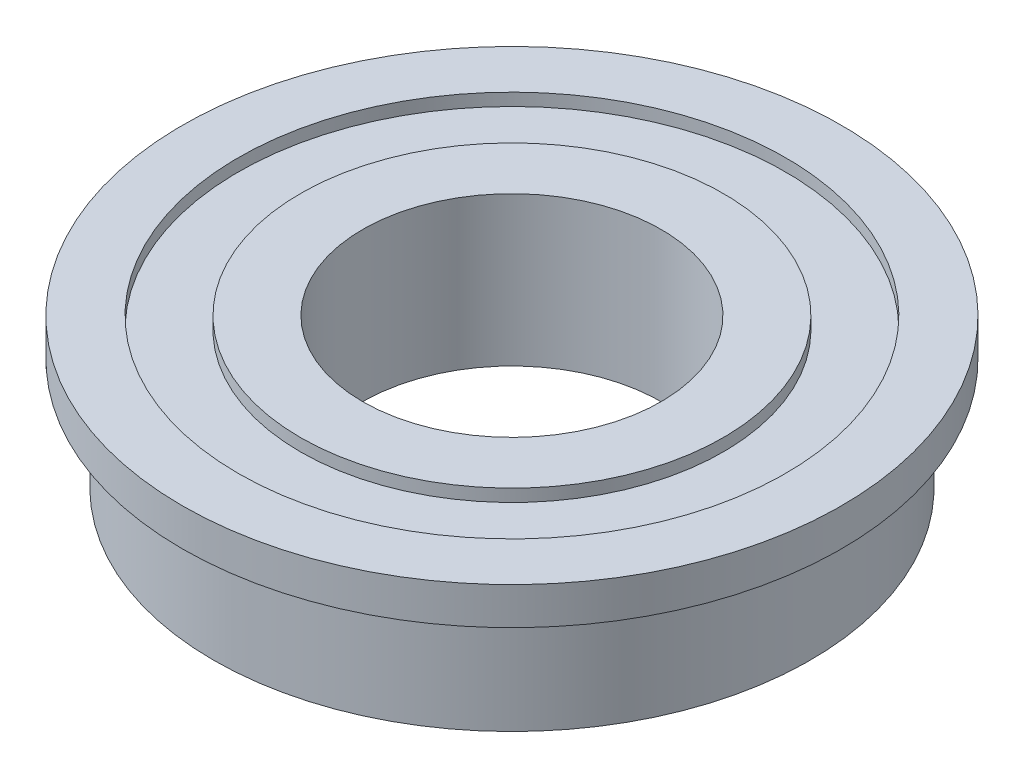
SolidWorks part; units mm, degrees
material "AISI 316 Stainless Steel Sheet (SS)"
ref_plane "Front Plane" through (0, 0, 0) normal (0, 0, 1) x (1, 0, 0)
ref_plane "Top Plane" through (0, 0, 0) normal (0, 1, 0) x (1, 0, 0)
ref_plane "Right Plane" through (0, 0, 0) normal (1, 0, 0) x (0, 0, -1)
sketch "Sketch1" plane through (0, 0, 0) normal (0, 1, 0) x (1, 0, 0)
  circle A0 centre (0, 0) radius 12
  circle A1 centre (0, 0) radius 13.25
  circle A2 centre (0, 0) radius 6
  dimension "D1" = 26.5
  dimension "D2" = 24
  dimension "D3" = 12
extrude "Boss-Extrude1" add sketch "Sketch1" against normal blind 6 contours A0 A2 region at (-11.6606, 0, 0)
extrude "Boss-Extrude2" add sketch "Sketch1<3>" against normal blind 1.5 contours A1 A0 region at (-12.8752, 0, 0)
sketch "Sketch1<3>" plane through (0, 0, 0) normal (0, 1, 0) x (1, 0, 0) same geometry as "Sketch1"
sketch "Sketch2" plane through (0, 0, 0) normal (0, 1, 0) x (1, 0, 0)
  circle A0 centre (0, 0) radius 8.5
  circle A2 centre (0, 0) radius 11
  dimension "D1" = 17
  dimension "D2" = 22
extrude "Cut-Extrude1" cut sketch "Sketch2" against normal blind 0.5
sketch "Sketch3" plane through (0, -6, 0) normal (0, -1, 0) x (1, 0, 0)
  circle A0 centre (0, 0) radius 8.5
  circle A1 centre (0, 0) radius 11
  circle A2 centre (0, 0) radius 11 construction
  circle A3 centre (0, 0) radius 8.5 construction
extrude "Cut-Extrude2" cut sketch "Sketch3" against normal blind 0.5
